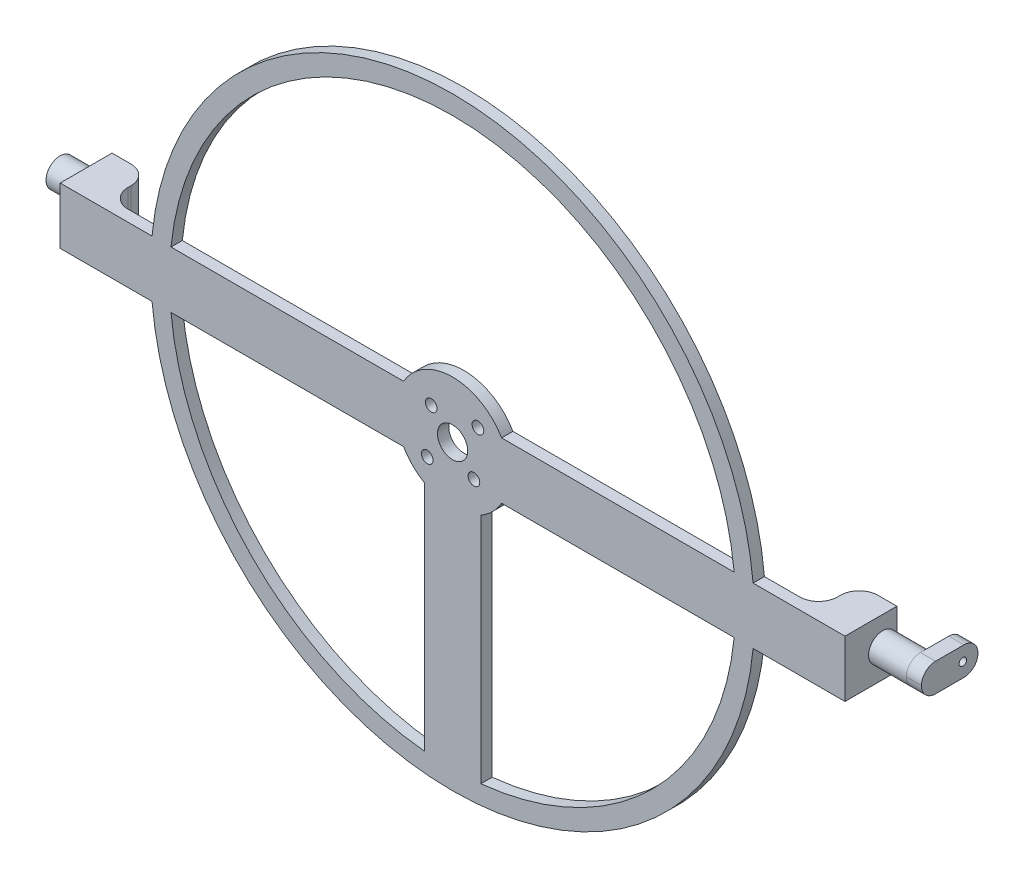
SolidWorks part; units mm, degrees
note: The reader was unsure of these and kept them because the rebuilt part matched: shared geometry of "Sketch1<3>".
ref_plane "Front Plane" through (0, 0, 0) normal (0, 0, 1) x (1, 0, 0)
ref_plane "Top Plane" through (0, 0, 0) normal (0, 1, 0) x (1, 0, 0)
ref_plane "Right Plane" through (0, 0, 0) normal (1, 0, 0) x (0, 0, -1)
sketch "Sketch1" plane through (0, 0, 0) normal (0, 0, 1) x (1, 0, 0)
  line L0 (12.9904, -7.5) -> (74.6241, -7.5)
  line L1 (12.9904, 7.5) -> (74.6241, 7.5)
  line L2 (-12.9904, 7.5) -> (-74.6241, 7.5)
  line L3 (-12.9904, -7.5) -> (-74.6241, -7.5)
  line L4 (7.5, -12.9904) -> (7.5, -74.6241)
  line L5 (-7.5, -12.9904) -> (-7.5, -74.6241)
  line L6 (79.6477, 7.5) -> (104, 7.5)
  line L7 (104, 7.5) -> (104, -7.5)
  line L8 (104, -7.5) -> (79.6477, -7.5)
  line L9 (-79.6477, 7.5) -> (-104, 7.5)
  line L10 (-104, 7.5) -> (-104, -7.5)
  line L11 (-104, -7.5) -> (-79.6477, -7.5)
  circle A0 centre (0, 0) radius 75
  arc A1 (79.8413, -5.0368) -> (79.8528, -4.8505) centre (0, 0) ccw
  circle A2 centre (0, 0) radius 15
  arc A4 (79.8249, 5.29) -> (-79.8222, 5.331) centre (0, 0) ccw
  arc A5 (-79.8222, 5.331) -> (-79.8343, 5.1465) centre (0, 0) ccw
  arc A6 (-79.8236, -5.3093) -> (79.8413, -5.0368) centre (0, 0) ccw
  dimension "D1" = 150
  dimension "D2" = 5
  dimension "D3" = 30
  dimension "D5" = 7.5
  dimension "D16" = 5
  dimension "D4" = 15
  dimension "D6" = 15
  dimension "D7" = 7.5
  dimension "D8" = 15
  dimension "D9" = 7.5
  dimension "D10" = 90
  dimension "D11" = 180
  dimension "D12" = 104
  dimension "D13" = 15
  dimension "D14" = 0
  dimension "D15" = 104
  dimension "D17" = 15
extrude "Boss-Extrude1" add sketch "Sketch1" along normal blind 3 contours A1 A0
extrude "Boss-Extrude2" add sketch "Sketch1<3>" along normal blind 3 contours A2 L2 A0 L3 | A2 | A2 L5 A0 L4 | A2 L0 A0 L1
sketch "Sketch1<3>" plane through (0, 0, 0) normal (0, 0, 1) x (1, 0, 0) same geometry as "Sketch1"
sketch "Sketch2" plane through (0, 0, 3) normal (0, 0, 1) x (1, 0, 0)
  circle A0 centre (-5.6569, 5.6569) radius 1.55
  circle A1 centre (6.7175, 6.7175) radius 1.55
  circle A2 centre (5.6569, -5.6569) radius 1.55
  circle A3 centre (-6.7175, -6.7175) radius 1.55
  point P8 (0, 0)
  dimension "D1" = 3.1
  dimension "D2" = 3.1
  dimension "D3" = 3.1
  dimension "D4" = 3.1
  dimension "D5" = 19
  dimension "D6" = 16
  dimension "D7" = 9.5
  dimension "D8" = 8
extrude "Cut-Extrude1" cut sketch "Sketch2" against normal blind 5
sketch "Sketch3" plane through (104, 0, 0) normal (1, 0, 0) x (0, 0, -1)
  line L0 (-3, 7.5) -> (-3, -7.5) construction
  circle A0 centre (7, 0) radius 3.75
  dimension "D1" = 7.5
  dimension "D2" = 10
sketch "Sketch4" plane through (-104, 0, 0) normal (-1, 0, 0) x (0, 0, 1)
  line L0 (3, 7.5) -> (3, -7.5) construction
  circle A0 centre (-7, 0) radius 3.75
  dimension "D1" = 7.5
  dimension "D2" = 10
extrude "Boss-Extrude3" add sketch "Sketch4" along normal blind 10
extrude "Boss-Extrude4" add sketch "Sketch3" along normal blind 10
sketch "Sketch5" plane through (114, 0, 0) normal (1, 0, 0) x (0, 0, -1)
  line L1 (18.25, 3.75) -> (3.25, 3.75)
  line L2 (18.25, 3.75) -> (18.25, -3.75)
  line L3 (18.25, -3.75) -> (3.25, -3.75)
  line L4 (3.25, 3.75) -> (3.25, -3.75)
  circle A1 centre (7, 0) radius 3.75 construction
  dimension "D1" = 7.5
  dimension "D2" = 3.75
  dimension "D3" = 3.75
  dimension "D4" = 15
extrude "Boss-Extrude5" add sketch "Sketch5" along normal blind 4
fillet "Fillet2" radius 3.75 4 edges at (116, -3.75, -3.25) (116, 3.75, -3.25) (116, 3.75, -18.25) (116, -3.75, -18.25)
sketch "Sketch6" plane through (118, 0, 0) normal (1, 0, 0) x (0, 0, -1)
  circle A0 centre (14.25, 0) radius 1
  dimension "D1" = 2
  dimension "D2" = 4
sketch "Sketch7" plane through (0, -7.5, 0) normal (0, -1, 0) x (1, 0, 0)
  line L0 (-104, 0) -> (-104, -10.75)
  line L1 (-104, -10.75) -> (-94, -10.75)
  line L2 (-94, -10.75) -> (-94, 0)
  line L3 (-104, 0) -> (-79.6477, 0) construction
  line L4 (-94, 0) -> (-104, 0)
  dimension "D1" = 10
  dimension "D2" = 10.75
sketch "Sketch8" plane through (0, -7.5, 0) normal (0, -1, 0) x (1, 0, 0)
  line L0 (104, 0) -> (104, -10.75)
  line L1 (104, -10.75) -> (94, -10.75)
  line L2 (94, -10.75) -> (94, 0)
  line L3 (104, 0) -> (79.6477, 0) construction
  line L4 (94, 0) -> (104, 0)
  dimension "D1" = 10.75
  dimension "D2" = 10
extrude "Boss-Extrude7" add sketch "Sketch8" against normal blind 15
fillet "Fillet4" radius 5 2 edges at (94, 0, -10.75)
extrude "Boss-Extrude6" add sketch "Sketch7" against normal blind 15
fillet "Fillet3" radius 5 2 edges at (-94, 0, -10.75) (-94, 0, 0)
extrude "Cut-Extrude4" cut sketch "Sketch6" against normal blind 4
sketch "Sketch9" plane through (0, 0, 0) normal (0, 0, -1) x (-1, 0, 0)
  circle A0 centre (0, 0) radius 4
  dimension "D1" = 8
extrude "Cut-Extrude5" cut sketch "Sketch9" against normal blind 4
